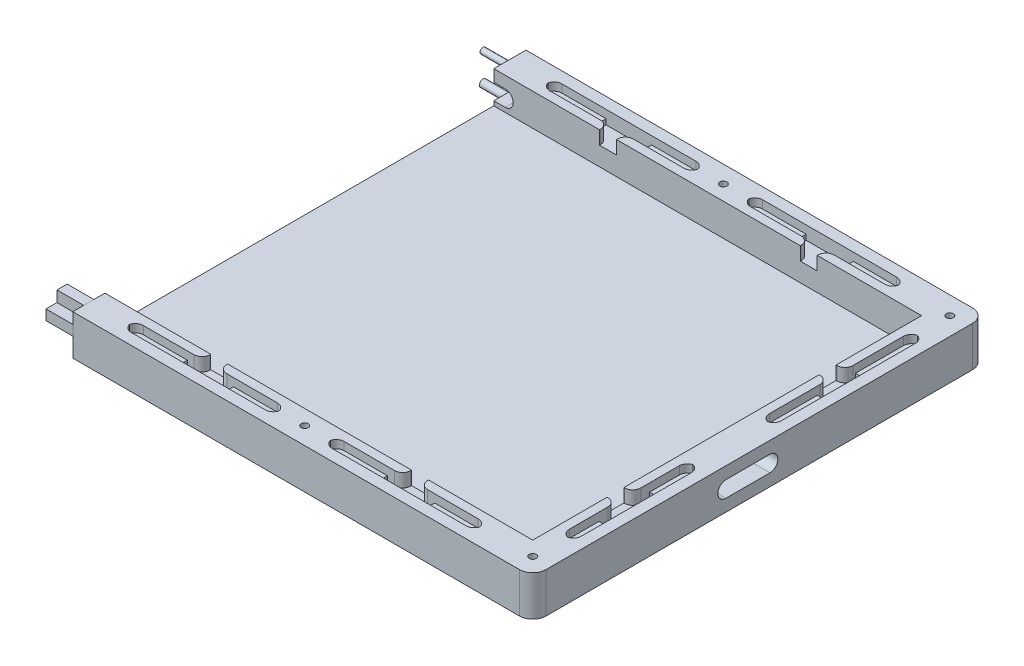
SolidWorks part; units mm, degrees
ref_plane "Front Plane" through (0, 0, 0) normal (0, 0, 1) x (1, 0, 0)
ref_plane "Top Plane" through (0, 0, 0) normal (0, 1, 0) x (1, 0, 0)
ref_plane "Right Plane" through (0, 0, 0) normal (1, 0, 0) x (0, 0, -1)
sketch "Sketch1" plane through (0, 0, 0) normal (0, 1, 0) x (1, 0, 0)
  line L0 (0, 152.7185) -> (0, -149.9342) construction
  line L1 (-90.768, 0) -> (299.0331, 0) construction
  line L2 (0, 72.5) -> (159.54, 72.5)
  line L3 (159.54, 72.5) -> (159.54, -72.5)
  line L4 (159.54, -72.5) -> (0, -72.5)
  line L5 (0, -72.5) -> (0, 72.5)
  dimension "D1" = 159.54
  dimension "D2" = 145
extrude "Boss-Extrude1" add sketch "Sketch1" along normal blind 3
sketch "Sketch3" plane through (0, 0, 0) normal (0, 1, 0) x (1, 0, 0)
  line L0 (0, 105.5814) -> (0, -111.8381) construction
  line L1 (-76.2859, 0) -> (270.0575, 0) construction
  line L2 (0, 72.5) -> (0, 84.5)
  line L3 (0, 84.5) -> (171.54, 84.5)
  line L4 (171.54, 84.5) -> (171.54, -84.5)
  line L5 (171.54, -84.5) -> (0, -84.5)
  line L6 (0, -84.5) -> (0, -72.5)
  line L7 (0, -72.5) -> (159.54, -72.5)
  line L8 (159.54, -72.5) -> (159.54, 72.5)
  line L9 (159.54, 72.5) -> (0, 72.5)
  dimension "D1" = 12
  dimension "D2" = 12
  dimension "D3" = 12
extrude "Boss-Extrude2" add sketch "Sketch3" along normal blind 15
sketch "Sketch4" plane through (0, 15, 0) normal (0, 1, 0) x (1, 0, 0)
  line L0 (45.75, 75.8) -> (45.75, 72.5)
  line L1 (70.6, 75.8) -> (45.75, 75.8)
  line L2 (70.6, 80.3) -> (70.6, 75.8)
  line L3 (14.6, 80.3) -> (70.6, 80.3)
  line L4 (14.6, 75.8) -> (14.6, 80.3)
  line L5 (39.45, 75.8) -> (14.6, 75.8)
  line L6 (39.45, 72.5) -> (39.45, 75.8)
  line L7 (45.75, 72.5) -> (39.45, 72.5)
  line L8 (120.64, 75.8) -> (120.64, 72.5)
  line L9 (145.49, 75.8) -> (120.64, 75.8)
  line L10 (145.49, 80.3) -> (145.49, 75.8)
  line L11 (89.49, 80.3) -> (145.49, 80.3)
  line L12 (89.49, 75.8) -> (89.49, 80.3)
  line L13 (114.34, 75.8) -> (89.49, 75.8)
  line L14 (114.34, 72.5) -> (114.34, 75.8)
  line L15 (120.64, 72.5) -> (114.34, 72.5)
  line L16 (0, 72.5) -> (159.54, 72.5) construction
  line L17 (0, 84.5) -> (0, 72.5) construction
  line L18 (159.54, 72.5) -> (159.54, -72.5) construction
  line L19 (0, 72.5) -> (0, -72.5) construction
  line L20 (145.49, -75.8) -> (120.64, -75.8)
  line L21 (145.49, -80.3) -> (145.49, -75.8)
  line L22 (89.49, -80.3) -> (145.49, -80.3)
  line L23 (89.49, -75.8) -> (89.49, -80.3)
  line L24 (114.34, -75.8) -> (89.49, -75.8)
  line L25 (114.34, -72.5) -> (114.34, -75.8)
  line L26 (120.64, -72.5) -> (114.34, -72.5)
  line L27 (120.64, -75.8) -> (120.64, -72.5)
  line L28 (70.6, -75.8) -> (45.75, -75.8)
  line L29 (70.6, -80.3) -> (70.6, -75.8)
  line L30 (14.6, -80.3) -> (70.6, -80.3)
  line L31 (14.6, -75.8) -> (14.6, -80.3)
  line L32 (39.45, -75.8) -> (14.6, -75.8)
  line L33 (39.45, -72.5) -> (39.45, -75.8)
  line L34 (45.75, -72.5) -> (39.45, -72.5)
  line L35 (45.75, -75.8) -> (45.75, -72.5)
  line L36 (159.54, -72.5) -> (0, -72.5) construction
  line L40 (159.54, -38.5) -> (162.84, -38.5)
  line L49 (159.54, 40.6) -> (162.84, 40.6)
  line L50 (162.84, 40.6) -> (162.84, 65.45)
  line L51 (162.84, 65.45) -> (167.34, 65.45)
  line L52 (167.34, 65.45) -> (167.34, 9.45)
  line L53 (167.34, 9.45) -> (162.84, 9.45)
  line L54 (162.84, 34.3) -> (162.84, 9.45)
  line L55 (159.54, 34.3) -> (162.84, 34.3)
  line L56 (159.54, 40.6) -> (159.54, 34.3)
  line L57 (162.84, -38.5) -> (162.84, -18.15)
  line L58 (162.84, -18.15) -> (167.34, -18.15)
  line L59 (167.34, -18.15) -> (167.34, -65.15)
  line L60 (167.34, -65.15) -> (162.84, -65.15)
  line L61 (162.84, -44.8) -> (162.84, -65.15)
  line L62 (159.54, -44.8) -> (162.84, -44.8)
  line L63 (159.54, -38.5) -> (159.54, -44.8)
  line L64 (0, -72.5) -> (159.54, -72.5) construction
  dimension "D1" = 6.3
  dimension "D2" = 3.3
  dimension "D3" = 4.5
  dimension "D4" = 56
  dimension "D5" = 6.3
  dimension "D6" = 3.3
  dimension "D7" = 4.5
  dimension "D8" = 56
  dimension "D9" = 0
  dimension "D10" = 0
  dimension "D11" = 39.45
  dimension "D12" = 38.9
  dimension "D13" = 56
  dimension "D14" = 39.45
  dimension "D15" = 38.9
  dimension "D16" = 0
  dimension "D17" = 31.9
  dimension "D18" = 6.3
  dimension "D19" = 56
  dimension "D20" = 27.7
  dimension "D21" = 6.3
  dimension "D22" = 47
  dimension "D23" = 56
  dimension "D24" = 3.3
  dimension "D25" = 6.3
  dimension "D26" = 6.3
  dimension "D27" = 3.3
  dimension "D28" = 4.5
  dimension "D29" = 4.5
  dimension "D30" = 3.3
  dimension "D31" = 4.5
  dimension "D32" = 3.3
  dimension "D33" = 4.5
extrude "Cut-Extrude1" cut sketch "Sketch4" against normal blind 3
sketch "Sketch5" plane through (0, 12, 0) normal (0, 1, 0) x (1, 0, 0)
  line L0 (39.45, -75.8) -> (28.5461, -75.8) construction
  line L1 (45.75, -75.8) -> (56.6539, -75.8) construction
  line L2 (39.45, -72.5) -> (39.45, -75.8)
  line L3 (39.45, -75.8) -> (33.9981, -75.8)
  line L4 (33.9981, -75.8) -> (33.9981, -80.3)
  line L5 (33.9981, -80.3) -> (51.2019, -80.3)
  line L6 (51.2019, -80.3) -> (51.2019, -75.8)
  line L7 (45.75, -72.5) -> (39.45, -72.5)
  line L8 (45.75, -72.5) -> (45.75, -75.8)
  line L9 (45.75, -75.8) -> (51.2019, -75.8)
  line L10 (114.34, -75.8) -> (103.0697, -75.8) construction
  line L11 (120.64, -75.8) -> (131.9103, -75.8) construction
  line L12 (114.34, -75.8) -> (108.7049, -75.8)
  line L13 (108.7049, -75.8) -> (108.7049, -80.3)
  line L14 (108.7049, -80.3) -> (126.2751, -80.3)
  line L15 (126.2751, -80.3) -> (126.2751, -75.8)
  line L16 (126.2751, -75.8) -> (120.64, -75.8)
  line L17 (120.64, -75.8) -> (120.64, -72.5)
  line L18 (120.64, -72.5) -> (114.34, -72.5)
  line L19 (114.34, -72.5) -> (114.34, -75.8)
  line L20 (0, -72.5) -> (159.54, -72.5) construction
  line L22 (14.6, -80.3) -> (70.6, -80.3) construction
  line L23 (70.6, -75.8) -> (45.75, -75.8) construction
  line L24 (42.6, -68.4649) -> (42.6, -82.099) construction
  line L26 (89.49, -80.3) -> (145.49, -80.3) construction
  line L27 (114.34, -75.8) -> (89.49, -75.8) construction
  line L28 (117.49, -70.6619) -> (117.49, -81.6393) construction
  line L29 (-14.3619, 0) -> (206.3964, 0) construction
  line L31 (120.64, 72.5) -> (114.34, 72.5)
  line L38 (45.75, 72.5) -> (39.45, 72.5)
  line L48 (159.54, -72.5) -> (159.54, 72.5) construction
  line L49 (159.54, 34.3) -> (162.84, 34.3) construction
  line L56 (162.84, 40.6) -> (159.54, 40.6) construction
  line L59 (157.6179, 36.6875) -> (170.3436, 36.6875) construction
  line L66 (96.0172, 13.3148) -> (96.0172, -25.9889) construction
  line L70 (159.54, -44.8) -> (159.54, -38.5)
  line L75 (159.54, 40.6) -> (162.84, 40.6)
  line L81 (159.54, 34.3) -> (162.84, 34.3)
  line L82 (159.54, 40.6) -> (159.54, 34.3)
  line L94 (158.2993, -40.5875) -> (170.1106, -40.5875) construction
  line L96 (120.64, 72.5) -> (120.64, 75.8)
  line L97 (120.64, 75.8) -> (126.3086, 75.8)
  line L98 (120.64, 75.8) -> (145.49, 75.8) construction
  line L99 (126.3086, 75.8) -> (126.3086, 80.3)
  line L100 (45.75, 72.5) -> (45.75, 75.8)
  line L101 (45.75, 75.8) -> (51.0897, 75.8)
  line L102 (45.75, 75.8) -> (70.6, 75.8) construction
  line L103 (51.0897, 75.8) -> (51.0897, 80.3)
  line L104 (70.6, 80.3) -> (14.6, 80.3) construction
  line L105 (51.0897, 80.3) -> (34.1103, 80.3)
  line L106 (70.6, 80.3) -> (14.6, 80.3) construction
  line L107 (34.1103, 80.3) -> (34.1103, 75.8)
  line L108 (14.6, 75.8) -> (39.45, 75.8) construction
  line L109 (34.1103, 75.8) -> (39.45, 75.8)
  line L110 (39.45, 75.8) -> (39.45, 72.5)
  line L112 (145.49, 80.3) -> (89.49, 80.3) construction
  line L115 (126.3086, 80.3) -> (108.7049, 80.3)
  line L116 (108.7049, 80.3) -> (108.7049, 75.8)
  line L117 (89.49, 75.8) -> (114.34, 75.8) construction
  line L118 (108.7049, 75.8) -> (114.34, 75.8)
  line L119 (114.34, 75.8) -> (114.34, 72.5)
  line L120 (162.84, 40.6) -> (162.84, 44.5797)
  line L121 (162.84, 65.45) -> (162.84, 40.6) construction
  line L122 (162.84, 44.5797) -> (167.34, 44.5797)
  line L123 (167.34, 9.45) -> (167.34, 65.45) construction
  line L124 (167.34, 44.5797) -> (167.34, 30.3203)
  line L125 (167.34, 9.45) -> (167.34, 65.45) construction
  line L126 (167.34, 30.3203) -> (162.84, 30.3203)
  line L127 (162.84, 34.3) -> (162.84, 9.45) construction
  line L128 (162.84, 30.3203) -> (162.84, 34.3)
  line L129 (159.54, -38.5) -> (162.84, -38.5)
  line L130 (162.84, -38.5) -> (162.84, -32.2059)
  line L131 (162.84, -18.15) -> (162.84, -38.5) construction
  line L132 (162.84, -32.2059) -> (167.34, -32.2059)
  line L133 (167.34, -65.15) -> (167.34, -18.15) construction
  line L134 (167.34, -32.2059) -> (167.34, -51.0941)
  line L135 (167.34, -65.15) -> (167.34, -18.15) construction
  line L136 (167.34, -51.0941) -> (162.84, -51.0941)
  line L137 (162.84, -44.8) -> (162.84, -65.15) construction
  line L138 (162.84, -51.0941) -> (162.84, -44.8)
  line L139 (162.84, -44.8) -> (159.54, -44.8)
extrude "Cut-Extrude2" cut sketch "Sketch5" against normal blind 2
sketch "Sketch6" plane through (171.54, 0, 0) normal (1, 0, 0) x (0, 0, -1)
  line L0 (-12.45, 10.5) -> (3.93, 10.5)
  line L1 (-12.45, 4.5) -> (3.93, 4.5)
  line L2 (-15.45, 5.5661) -> (-15.45, 9.4339) construction
  line L5 (-84.5, 7.5) -> (84.5, 7.5) construction
  line L6 (-84.5, 15) -> (-84.5, 0) construction
  line L7 (84.5, 15) -> (84.5, 0) construction
  arc A0 (-12.45, 4.5) -> (-12.45, 10.5) centre (-12.45, 7.5) cw
  arc A1 (3.93, 10.5) -> (3.93, 4.5) centre (3.93, 7.5) cw
  point P6 (-12.45, 10.5)
  point P9 (-15.45, 7.5)
  dimension "D2" = 3
  dimension "D1" = 16.38
  dimension "D3" = 69.05
extrude "Cut-Extrude3" cut sketch "Sketch6" against normal blind 12
sketch "Sketch7" plane through (0, 0, -84.5) normal (0, 0, -1) x (-1, 0, 0)
  line L0 (31.7354, 7.6343) -> (-33.2248, 7.6343) construction
  line L1 (-4.24, 10.6343) -> (12.14, 10.6343)
  line L2 (-4.24, 4.6343) -> (12.14, 4.6343)
  line L3 (-7.24, 4.7002) -> (-7.24, 10.5684) construction
  line L4 (0, 15) -> (0, 0) construction
  line L5 (-171.54, 0) -> (0, 0) construction
  arc A0 (-4.24, 4.6343) -> (-4.24, 10.6343) centre (-4.24, 7.6343) cw
  arc A1 (12.14, 10.6343) -> (12.14, 4.6343) centre (12.14, 7.6343) cw
  point P8 (-4.24, 10.6343)
  point P11 (-7.24, 7.6343)
  dimension "D2" = 3
  dimension "D1" = 16.38
  dimension "D3" = 7.24
  dimension "D4" = 7.6343
extrude "Cut-Extrude4" cut sketch "Sketch7" against normal blind 12
sketch "Sketch8" plane through (0, 0, 0) normal (-1, 0, 0) x (0, 0, 1)
  line L0 (-78.5, 4.6343) -> (-78.5, 0.0234) construction
  line L1 (-72.5, 4.6343) -> (-84.5, 4.6343) construction
  line L2 (-84.5, 12.8171) -> (-72.5, 12.8171) construction
  line L3 (-84.5, 15) -> (-84.5, 10.6343) construction
  line L4 (-72.5, 15) -> (-72.5, 10.6343) construction
  circle A0 centre (-78.5, 12.8171) radius 1.1
  circle A1 centre (-78.5, 2.3288) radius 1.35
  dimension "D1" = 2.2
  dimension "D2" = 2.7
extrude "Boss-Extrude3" add sketch "Sketch8" along normal blind 10
sketch "Sketch9" plane through (0, 0, 0) normal (-1, 0, 0) x (0, 0, 1)
  line L2 (72.5, 9) -> (84.5, 9) construction
  line L3 (72.5, 15) -> (72.5, 3) construction
  line L4 (84.5, 15) -> (84.5, 0) construction
  line L5 (72.5, 3) -> (84.5, 3) construction
  line L6 (78.5, 15) -> (78.5, 3) construction
  line L7 (72.5, 15) -> (84.5, 15) construction
  line L8 (84.4892, 3.011) -> (84.4892, 14.989) construction
  line L9 (84.4892, 14.989) -> (72.5108, 14.989) construction
  line L10 (72.5108, 14.989) -> (72.5117, 3.011) construction
  line L11 (72.5117, 3.011) -> (84.4892, 3.011) construction
  line L12 (84.4892, 3.011) -> (72.5108, 14.989) construction
  line L13 (72.5108, 14.989) -> (84.4892, 14.989) construction
  line L14 (84.4892, 14.989) -> (72.5117, 3.011) construction
  line L15 (78.5, 15.1883) -> (78.5, 3.011) construction
  line L16 (72.5112, 9) -> (83.4994, 9) construction
  line L17 (76.6, 14.989) -> (80.4, 14.989)
  line L18 (84.4892, 7.1) -> (84.4892, 10.9)
  line L19 (80.4, 3.011) -> (76.6, 3.011)
  line L20 (72.5114, 7.1) -> (72.5111, 10.9)
  line L21 (76.6, 14.989) -> (76.6, 10.9)
  line L22 (76.6, 10.9) -> (72.5111, 10.9)
  line L23 (72.5114, 7.1) -> (76.6, 7.1)
  line L24 (76.6, 7.1) -> (76.6, 3.011)
  line L25 (80.4, 3.011) -> (80.4, 7.1)
  line L26 (80.4, 7.1) -> (84.4892, 7.1)
  line L27 (84.4892, 10.9) -> (80.4, 10.9)
  line L28 (80.4, 10.9) -> (80.4, 14.989)
  line L29 (78.5, 9) -> (78.5, 14.989) construction
  line L30 (84.4892, 9) -> (72.5112, 9) construction
  point P26 (78.5, 14.989)
  point P30 (84.4892, 9)
  point P33 (78.5, 3.011)
  point P36 (72.5112, 9)
  point P43 (78.5, 9)
  dimension "D1" = 3.8
  dimension "D2" = 3.8
  dimension "D3" = 3.8
  dimension "D4" = 3.8
  dimension "D5" = 0
extrude "Boss-Extrude5" add sketch "Sketch9" along normal blind 10
fillet "Fillet3" radius 5 1 edges at (171.54, 7.5, 84.5)
fillet "Fillet4" radius 5 1 edges at (171.54, 7.5, -84.5)
sketch "Sketch10" plane through (0, 0, 0) normal (0, -1, 0) x (1, 0, 0)
  circle A0 centre (80.0525, 78.05) radius 1.325
  circle A1 centre (164.8078, 77.7678) radius 1.325
  circle A2 centre (164.8078, -77.7678) radius 1.325
  circle A3 centre (80.0525, -78.05) radius 1.325
  dimension "D1" = 2.65
  dimension "D2" = 2.65
  dimension "D3" = 2.65
  dimension "D4" = 2.65
extrude "Cut-Extrude5" cut sketch "Sketch10" against normal blind 17
sketch "Sketch12" plane through (0, 0, 0) normal (0, -1, 0) x (-1, 0, 0)
  circle A0 centre (-80.0525, -78.05) radius 3
  circle A1 centre (-164.8078, -77.7678) radius 3
  circle A2 centre (-164.8078, 77.7678) radius 3
  circle A3 centre (-80.0525, 78.05) radius 3
  dimension "D1" = 6
  dimension "D2" = 6
  dimension "D3" = 6
  dimension "D4" = 6
extrude "Cut-Extrude6" cut sketch "Sketch12" against normal blind 8
sketch "Sketch13" plane through (0, 0, 0) normal (0, -1, 0) x (1, 0, 0)
  line L0 (80.0525, 78.05) -> (164.8078, 77.7678) construction
  line L1 (122.4301, 77.9089) -> (121.9108, -78.05) construction
  line L2 (80.0525, -64.5) -> (151.54, -64.5) construction
  line L3 (166.54, -84.5) -> (0, -84.5) construction
  line L4 (80.0525, 64.5) -> (151.54, 64.5) construction
  line L5 (0, 84.5) -> (166.54, 84.5) construction
  line L6 (171.54, 79.5) -> (171.54, -79.5) construction
  line L7 (151.54, 64.5) -> (151.54, 84.5) construction
  circle A0 centre (151.54, 64.5) radius 6.25
  circle A1 centre (151.54, -64.5) radius 6.25
  point P18 (151.54, 64.5)
  point P19 (151.54, -64.5)
  dimension "D5" = 12.5
  dimension "D6" = 12.5
  dimension "D1" = 20
  dimension "D2" = 20
  dimension "D3" = 20
  dimension "D4" = 20
extrude "Cut-Extrude7" cut sketch "Sketch13" against normal blind 1
fillet "Fillet5" radius 3 12 edges at (45.75, 12.5, -75.8) (39.45, 12.5, -75.8) (120.64, 12.5, -75.8) (114.34, 12.5, -75.8) (162.84, 12.5, -34.3) (162.84, 12.5, -40.6) (162.84, 12.5, 44.8) (162.84, 12.5, 38.5) (120.64, 12.5, 75.8) (114.34, 12.5, 75.8) (45.75, 12.5, 75.8) (39.45, 12.5, 75.8)
fillet "Fillet6" radius 3 24 edges at (70.6, 13.5, 75.8) (70.6, 13.5, 80.3) (14.6, 13.5, 75.8) (14.6, 13.5, 80.3) (89.49, 13.5, 80.3) (89.49, 13.5, 75.8) (145.49, 13.5, 80.3) (145.49, 13.5, 75.8) (167.34, 13.5, 18.15) (162.84, 13.5, 18.15) (167.34, 13.5, 65.15) (162.84, 13.5, 65.15) (167.34, 13.5, -9.45) (162.84, 13.5, -9.45) (167.34, 13.5, -65.45) (162.84, 13.5, -65.45) (145.49, 13.5, -80.3) (145.49, 13.5, -75.8) (89.49, 13.5, -75.8) (89.49, 13.5, -80.3) (70.6, 13.5, -75.8) (70.6, 13.5, -80.3) (14.6, 13.5, -80.3) (14.6, 13.5, -75.8)
